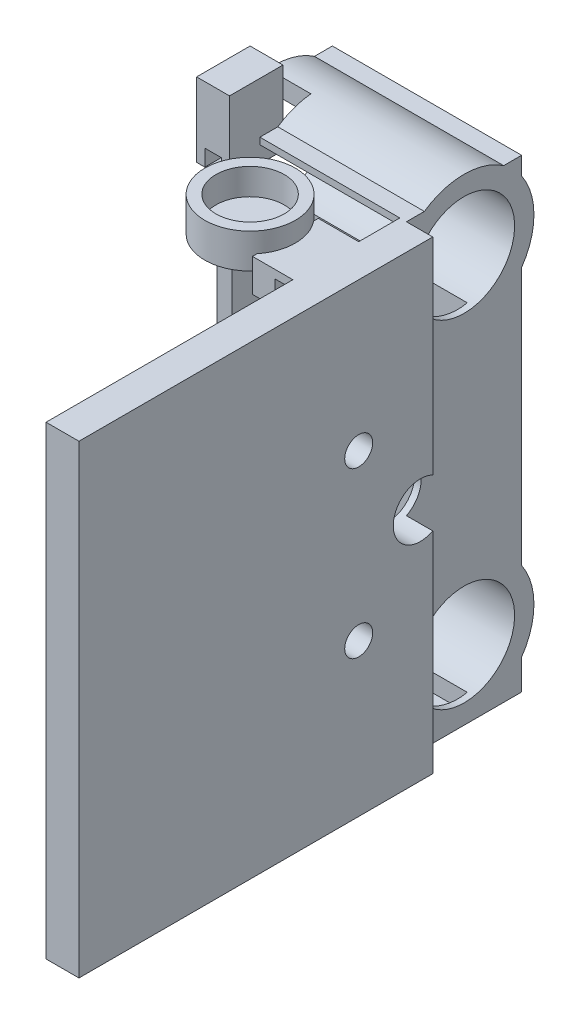
SolidWorks part; units mm, degrees
other "Preload Printed Carriage"
other "Steel core clearance tool"
other "Final core clearance tool"
other "Preload Printed Carriage Left"
ref_plane "Front Plane" through (0, 0, 0) normal (0, 0, 1) x (1, 0, 0)
ref_plane "Top Plane" through (0, 0, 0) normal (0, 1, 0) x (1, 0, 0)
ref_plane "Right Plane" through (0, 0, 0) normal (1, 0, 0) x (0, 0, -1)
sketch3d "Guide carrier body sketch datum points"
  point P0 (27.7083, -57, -35)
  point P1 (37.7083, -57, -35)
  point P2 (27.7083, -47, -35)
ref_plane "Guide carrier body sketch plane" through (0, 0, -35) normal (0, 0, 1) x (1, 0, 0)
sketch "Guide carrier body sketch" plane through (0, 0, -35) normal (0, 0, 1) x (1, 0, 0)
  line L0 (27.7083, -57) -> (50.7083, -57)
  line L1 (50.7083, -57) -> (50.7083, -0.5)
  line L2 (50.7083, -0.5) -> (27.7083, -0.5)
  line L3 (27.7083, -0.5) -> (27.7083, -57)
extrude "Guide carrier body" add sketch "Guide carrier body sketch" along normal blind 14 separate body
sketch3d "Rear clamp wall sketch datum points"
  point P0 (49.9083, -57, -21)
  point P1 (59.9083, -57, -21)
  point P2 (49.9083, -47, -21)
ref_plane "Rear clamp wall sketch plane" through (0, 0, -21) normal (0, 0, 1) x (1, 0, 0)
sketch "Rear clamp wall sketch" plane through (0, 0, -21) normal (0, 0, 1) x (1, 0, 0)
  line L0 (49.9083, -57) -> (53.9083, -57)
  line L1 (53.9083, -57) -> (53.9083, -0.5)
  line L2 (53.9083, -0.5) -> (49.9083, -0.5)
  line L3 (49.9083, -0.5) -> (49.9083, -57)
extrude "Rear clamp wall" add sketch "Rear clamp wall sketch" along normal blind 43
sketch3d "Guide bush boss 1 sketch datum points"
  point P0 (27.7083, -9, -28)
  point P1 (27.7083, 1, -28)
  point P2 (27.7083, -9, -18)
ref_plane "Guide bush boss 1 sketch plane" through (27.7083, 0, 0) normal (1, 0, 0) x (0, 0, -1)
sketch "Guide bush boss 1 sketch" plane through (27.7083, 0, 0) normal (1, 0, 0) x (0, 0, -1)
  circle A0 centre (28, -9) radius 8.5
extrude "Guide bush boss 1" add sketch "Guide bush boss 1 sketch" along normal blind 23
sketch3d "Guide bush boss 2 sketch datum points"
  point P0 (27.7083, -50, -28)
  point P1 (27.7083, -40, -28)
  point P2 (27.7083, -50, -18)
ref_plane "Guide bush boss 2 sketch plane" through (27.7083, 0, 0) normal (1, 0, 0) x (0, 0, -1)
sketch "Guide bush boss 2 sketch" plane through (27.7083, 0, 0) normal (1, 0, 0) x (0, 0, -1)
  circle A0 centre (28, -50) radius 8.5
extrude "Guide bush boss 2" add sketch "Guide bush boss 2 sketch" along normal blind 23
sketch3d "Steel tube cavity sketch datum points"
  point P0 (29.5083, -56.2, -29.2)
  point P1 (39.5083, -56.2, -29.2)
  point P2 (29.5083, -46.2, -29.2)
ref_plane "Steel tube cavity sketch plane" through (0, 0, -29.2) normal (0, 0, 1) x (1, 0, 0)
sketch "Steel tube cavity sketch" plane through (0, 0, -29.2) normal (0, 0, 1) x (1, 0, 0)
  line L0 (29.5083, -56.2) -> (49.9083, -56.2)
  line L1 (49.9083, -56.2) -> (49.9083, -0.8)
  line L2 (49.9083, -0.8) -> (29.5083, -0.8)
  line L3 (29.5083, -0.8) -> (29.5083, -56.2)
extrude "Steel tube cavity" cut sketch "Steel tube cavity sketch" along normal blind 40.4
sketch3d "Guide bush bore 1 sketch datum points"
  point P0 (27.6, -9, -28)
  point P1 (27.6, 1, -28)
  point P2 (27.6, -9, -18)
ref_plane "Guide bush bore 1 sketch plane" through (27.6, 0, 0) normal (1, 0, 0) x (0, 0, -1)
sketch "Guide bush bore 1 sketch" plane through (27.6, 0, 0) normal (1, 0, 0) x (0, 0, -1)
  circle A0 centre (28, -9) radius 6.15
extrude "Guide bush bore 1" cut sketch "Guide bush bore 1 sketch" along normal blind 23.3
sketch3d "Guide bush bore 2 sketch datum points"
  point P0 (27.6, -50, -28)
  point P1 (27.6, -40, -28)
  point P2 (27.6, -50, -18)
ref_plane "Guide bush bore 2 sketch plane" through (27.6, 0, 0) normal (1, 0, 0) x (0, 0, -1)
sketch "Guide bush bore 2 sketch" plane through (27.6, 0, 0) normal (1, 0, 0) x (0, 0, -1)
  circle A0 centre (28, -50) radius 6.15
extrude "Guide bush bore 2" cut sketch "Guide bush bore 2 sketch" along normal blind 23.3
sketch3d "Clamp bolt clearance 1 sketch datum points"
  point P0 (49.8, -19, -12)
  point P1 (49.8, -9, -12)
  point P2 (49.8, -19, -2)
ref_plane "Clamp bolt clearance 1 sketch plane" through (49.8, 0, 0) normal (1, 0, 0) x (0, 0, -1)
sketch "Clamp bolt clearance 1 sketch" plane through (49.8, 0, 0) normal (1, 0, 0) x (0, 0, -1)
  circle A0 centre (12, -19) radius 1.7
extrude "Clamp bolt clearance 1" cut sketch "Clamp bolt clearance 1 sketch" along normal blind 4.3
sketch3d "Clamp bolt clearance 2 sketch datum points"
  point P0 (49.8, -39, -12)
  point P1 (49.8, -29, -12)
  point P2 (49.8, -39, -2)
ref_plane "Clamp bolt clearance 2 sketch plane" through (49.8, 0, 0) normal (1, 0, 0) x (0, 0, -1)
sketch "Clamp bolt clearance 2 sketch" plane through (49.8, 0, 0) normal (1, 0, 0) x (0, 0, -1)
  circle A0 centre (12, -39) radius 1.7
extrude "Clamp bolt clearance 2" cut sketch "Clamp bolt clearance 2 sketch" along normal blind 4.3
sketch3d "Travel flag root sketch datum points"
  point P0 (28.7083, -59, -27)
  point P1 (38.7083, -59, -27)
  point P2 (28.7083, -49, -27)
ref_plane "Travel flag root sketch plane" through (0, 0, -27) normal (0, 0, 1) x (1, 0, 0)
sketch "Travel flag root sketch" plane through (0, 0, -27) normal (0, 0, 1) x (1, 0, 0)
  line L0 (28.7083, -59) -> (32.7083, -59)
  line L1 (32.7083, -59) -> (32.7083, -54)
  line L2 (32.7083, -54) -> (28.7083, -54)
  line L3 (28.7083, -54) -> (28.7083, -59)
extrude "Travel flag root" add sketch "Travel flag root sketch" along normal blind 6
sketch3d "Magnet holder bridge sketch datum points"
  point P0 (45, -57, -16)
  point P1 (55, -57, -16)
  point P2 (45, -47, -16)
ref_plane "Magnet holder bridge sketch plane" through (0, 0, -16) normal (0, 0, 1) x (1, 0, 0)
sketch "Magnet holder bridge sketch" plane through (0, 0, -16) normal (0, 0, 1) x (1, 0, 0)
  line L0 (45, -57) -> (53.908, -57)
  line L1 (53.908, -57) -> (53.908, -53)
  line L2 (53.908, -53) -> (45, -53)
  line L3 (45, -53) -> (45, -57)
extrude "Magnet holder bridge" add sketch "Magnet holder bridge sketch" along normal blind 8
sketch3d "Magnet holder boss sketch datum points"
  point P0 (40.708, -59.4, -12)
  point P1 (50.708, -59.4, -12)
  point P2 (40.708, -59.4, -22)
ref_plane "Magnet holder boss sketch plane" through (0, -59.4, 0) normal (0, 1, 0) x (1, 0, 0)
sketch "Magnet holder boss sketch" plane through (0, -59.4, 0) normal (0, 1, 0) x (1, 0, 0)
  circle A0 centre (40.708, 12) radius 5.5
extrude "Magnet holder boss" add sketch "Magnet holder boss sketch" along normal blind 4.2
sketch3d "Magnet seating pocket sketch datum points"
  point P0 (40.708, -59.5, -12)
  point P1 (50.708, -59.5, -12)
  point P2 (40.708, -59.5, -22)
ref_plane "Magnet seating pocket sketch plane" through (0, -59.5, 0) normal (0, 1, 0) x (1, 0, 0)
sketch "Magnet seating pocket sketch" plane through (0, -59.5, 0) normal (0, 1, 0) x (1, 0, 0)
  circle A0 centre (40.708, 12) radius 4.15
extrude "Magnet seating pocket" cut sketch "Magnet seating pocket sketch" along normal blind 3.3
sketch3d "Steel core clearance tool Steel tube stock sketch datum points"
  point P0 (29.7083, -56, -29)
  point P1 (39.7083, -56, -29)
  point P2 (29.7083, -46, -29)
ref_plane "Steel core clearance tool Steel tube stock sketch plane" through (0, 0, -29) normal (0, 0, 1) x (1, 0, 0)
sketch "Steel core clearance tool Steel tube stock sketch" plane through (0, 0, -29) normal (0, 0, 1) x (1, 0, 0)
  line L0 (29.7083, -56) -> (49.7083, -56)
  line L1 (49.7083, -56) -> (49.7083, -1)
  line L2 (49.7083, -1) -> (29.7083, -1)
  line L3 (29.7083, -1) -> (29.7083, -56)
extrude "Steel core clearance tool Steel tube stock" add sketch "Steel core clearance tool Steel tube stock sketch" along normal blind 40 separate body
sketch3d "Steel core clearance tool Tube interior sketch datum points"
  point P0 (31.7083, -56.1, -27)
  point P1 (41.7083, -56.1, -27)
  point P2 (31.7083, -46.1, -27)
ref_plane "Steel core clearance tool Tube interior sketch plane" through (0, 0, -27) normal (0, 0, 1) x (1, 0, 0)
sketch "Steel core clearance tool Tube interior sketch" plane through (0, 0, -27) normal (0, 0, 1) x (1, 0, 0)
  line L0 (31.7083, -56.1) -> (47.7083, -56.1)
  line L1 (47.7083, -56.1) -> (47.7083, -0.9)
  line L2 (47.7083, -0.9) -> (31.7083, -0.9)
  line L3 (31.7083, -0.9) -> (31.7083, -56.1)
extrude "Steel core clearance tool Tube interior" cut sketch "Steel core clearance tool Tube interior sketch" along normal blind 36
sketch3d "Steel core clearance tool Guide bush clearance 1 sketch datum points"
  point P0 (29.6, -9, -28)
  point P1 (29.6, 1, -28)
  point P2 (29.6, -9, -18)
ref_plane "Steel core clearance tool Guide bush clearance 1 sketch plane" through (29.6, 0, 0) normal (1, 0, 0) x (0, 0, -1)
sketch "Steel core clearance tool Guide bush clearance 1 sketch" plane through (29.6, 0, 0) normal (1, 0, 0) x (0, 0, -1)
  circle A0 centre (28, -9) radius 6.2
extrude "Steel core clearance tool Guide bush clearance 1" cut sketch "Steel core clearance tool Guide bush clearance 1 sketch" along normal blind 20.3
sketch3d "Steel core clearance tool Guide bush clearance 2 sketch datum points"
  point P0 (29.6, -50, -28)
  point P1 (29.6, -40, -28)
  point P2 (29.6, -50, -18)
ref_plane "Steel core clearance tool Guide bush clearance 2 sketch plane" through (29.6, 0, 0) normal (1, 0, 0) x (0, 0, -1)
sketch "Steel core clearance tool Guide bush clearance 2 sketch" plane through (29.6, 0, 0) normal (1, 0, 0) x (0, 0, -1)
  circle A0 centre (28, -50) radius 6.2
extrude "Steel core clearance tool Guide bush clearance 2" cut sketch "Steel core clearance tool Guide bush clearance 2 sketch" along normal blind 20.3
sketch3d "Steel core clearance tool Screw through clearance sketch datum points"
  point P0 (29.6, -29, -19.5)
  point P1 (29.6, -19, -19.5)
  point P2 (29.6, -29, -9.5)
ref_plane "Steel core clearance tool Screw through clearance sketch plane" through (29.6, 0, 0) normal (1, 0, 0) x (0, 0, -1)
sketch "Steel core clearance tool Screw through clearance sketch" plane through (29.6, 0, 0) normal (1, 0, 0) x (0, 0, -1)
  circle A0 centre (19.5, -29) radius 3.3
extrude "Steel core clearance tool Screw through clearance" cut sketch "Steel core clearance tool Screw through clearance sketch" along normal blind 20.3
sketch3d "Steel core clearance tool Spring pin clearance 1 sketch datum points"
  point P0 (35.7083, -12, 8.9)
  point P1 (45.7083, -12, 8.9)
  point P2 (35.7083, -2, 8.9)
ref_plane "Steel core clearance tool Spring pin clearance 1 sketch plane" through (0, 0, 8.9) normal (0, 0, 1) x (1, 0, 0)
sketch "Steel core clearance tool Spring pin clearance 1 sketch" plane through (0, 0, 8.9) normal (0, 0, 1) x (1, 0, 0)
  circle A0 centre (35.7083, -12) radius 1.7
extrude "Steel core clearance tool Spring pin clearance 1" cut sketch "Steel core clearance tool Spring pin clearance 1 sketch" along normal blind 2.2
sketch3d "Steel core clearance tool Spring pin clearance 2 sketch datum points"
  point P0 (35.7083, -29, 8.9)
  point P1 (45.7083, -29, 8.9)
  point P2 (35.7083, -19, 8.9)
ref_plane "Steel core clearance tool Spring pin clearance 2 sketch plane" through (0, 0, 8.9) normal (0, 0, 1) x (1, 0, 0)
sketch "Steel core clearance tool Spring pin clearance 2 sketch" plane through (0, 0, 8.9) normal (0, 0, 1) x (1, 0, 0)
  circle A0 centre (35.7083, -29) radius 1.7
extrude "Steel core clearance tool Spring pin clearance 2" cut sketch "Steel core clearance tool Spring pin clearance 2 sketch" along normal blind 2.2
sketch3d "Steel core clearance tool Spring pin clearance 3 sketch datum points"
  point P0 (35.7083, -46, 8.9)
  point P1 (45.7083, -46, 8.9)
  point P2 (35.7083, -36, 8.9)
ref_plane "Steel core clearance tool Spring pin clearance 3 sketch plane" through (0, 0, 8.9) normal (0, 0, 1) x (1, 0, 0)
sketch "Steel core clearance tool Spring pin clearance 3 sketch" plane through (0, 0, 8.9) normal (0, 0, 1) x (1, 0, 0)
  circle A0 centre (35.7083, -46) radius 1.7
extrude "Steel core clearance tool Spring pin clearance 3" cut sketch "Steel core clearance tool Spring pin clearance 3 sketch" along normal blind 2.2
sketch3d "Steel core clearance tool Clamp bolt clearance 1 sketch datum points"
  point P0 (47.6, -19, -12)
  point P1 (47.6, -9, -12)
  point P2 (47.6, -19, -2)
ref_plane "Steel core clearance tool Clamp bolt clearance 1 sketch plane" through (47.6, 0, 0) normal (1, 0, 0) x (0, 0, -1)
sketch "Steel core clearance tool Clamp bolt clearance 1 sketch" plane through (47.6, 0, 0) normal (1, 0, 0) x (0, 0, -1)
  circle A0 centre (12, -19) radius 1.7
extrude "Steel core clearance tool Clamp bolt clearance 1" cut sketch "Steel core clearance tool Clamp bolt clearance 1 sketch" along normal blind 2.3
sketch3d "Steel core clearance tool Clamp bolt clearance 2 sketch datum points"
  point P0 (47.6, -39, -12)
  point P1 (47.6, -29, -12)
  point P2 (47.6, -39, -2)
ref_plane "Steel core clearance tool Clamp bolt clearance 2 sketch plane" through (47.6, 0, 0) normal (1, 0, 0) x (0, 0, -1)
sketch "Steel core clearance tool Clamp bolt clearance 2 sketch" plane through (47.6, 0, 0) normal (1, 0, 0) x (0, 0, -1)
  circle A0 centre (12, -39) radius 1.7
extrude "Steel core clearance tool Clamp bolt clearance 2" cut sketch "Steel core clearance tool Clamp bolt clearance 2 sketch" along normal blind 2.3
combine bodies "Combine1" operation type subtract main body 113 bodies to subtract 123
sketch3d "Screw full travel clearance sketch datum points"
  point P0 (27.5, -29, -19.5)
  point P1 (27.5, -19, -19.5)
  point P2 (27.5, -29, -9.5)
ref_plane "Screw full travel clearance sketch plane" through (27.5, 0, 0) normal (1, 0, 0) x (0, 0, -1)
sketch "Screw full travel clearance sketch" plane through (27.5, 0, 0) normal (1, 0, 0) x (0, 0, -1)
  circle A0 centre (19.5, -29) radius 3.3
extrude "Screw full travel clearance" cut sketch "Screw full travel clearance sketch" along normal blind 26.7
sketch3d "Travel flag relief sketch datum points"
  point P0 (28.6, -59.2, -27.2)
  point P1 (38.6, -59.2, -27.2)
  point P2 (28.6, -49.2, -27.2)
ref_plane "Travel flag relief sketch plane" through (0, 0, -27.2) normal (0, 0, 1) x (1, 0, 0)
sketch "Travel flag relief sketch" plane through (0, 0, -27.2) normal (0, 0, 1) x (1, 0, 0)
  line L0 (28.6, -59.2) -> (32.9, -59.2)
  line L1 (32.9, -59.2) -> (32.9, -54)
  line L2 (32.9, -54) -> (28.6, -54)
  line L3 (28.6, -54) -> (28.6, -59.2)
extrude "Travel flag relief" cut sketch "Travel flag relief sketch" along normal blind 6.3
sketch3d "Clearanced travel flag sketch datum points"
  point P0 (28.7083, 0, 0)
  point P1 (28.7083, 10, 0)
  point P2 (28.7083, 0, 10)
ref_plane "Clearanced travel flag sketch plane" through (28.7083, 0, 0) normal (1, 0, 0) x (0, 0, -1)
sketch "Clearanced travel flag sketch" plane through (28.7083, 0, 0) normal (1, 0, 0) x (0, 0, -1)
  line L0 (17.5, -63) -> (24, -63)
  line L1 (24, -63) -> (24, -54.6715)
  line L2 (23.3285, -54) -> (17.5, -54)
  line L3 (17.5, -54) -> (17.5, -63)
  arc A0 (24, -54.6715) -> (23.3285, -54) centre (28, -50) cw
extrude "Clearanced travel stop flag" add sketch "Clearanced travel flag sketch" along normal blind 4
sketch3d "Final core clearance tool Steel tube stock sketch datum points"
  point P0 (29.7083, -56, -29)
  point P1 (39.7083, -56, -29)
  point P2 (29.7083, -46, -29)
ref_plane "Final core clearance tool Steel tube stock sketch plane" through (0, 0, -29) normal (0, 0, 1) x (1, 0, 0)
sketch "Final core clearance tool Steel tube stock sketch" plane through (0, 0, -29) normal (0, 0, 1) x (1, 0, 0)
  line L0 (29.7083, -56) -> (49.7083, -56)
  line L1 (49.7083, -56) -> (49.7083, -1)
  line L2 (49.7083, -1) -> (29.7083, -1)
  line L3 (29.7083, -1) -> (29.7083, -56)
extrude "Final core clearance tool Steel tube stock" add sketch "Final core clearance tool Steel tube stock sketch" along normal blind 40 separate body
sketch3d "Final core clearance tool Tube interior sketch datum points"
  point P0 (31.7083, -56.1, -27)
  point P1 (41.7083, -56.1, -27)
  point P2 (31.7083, -46.1, -27)
ref_plane "Final core clearance tool Tube interior sketch plane" through (0, 0, -27) normal (0, 0, 1) x (1, 0, 0)
sketch "Final core clearance tool Tube interior sketch" plane through (0, 0, -27) normal (0, 0, 1) x (1, 0, 0)
  line L0 (31.7083, -56.1) -> (47.7083, -56.1)
  line L1 (47.7083, -56.1) -> (47.7083, -0.9)
  line L2 (47.7083, -0.9) -> (31.7083, -0.9)
  line L3 (31.7083, -0.9) -> (31.7083, -56.1)
extrude "Final core clearance tool Tube interior" cut sketch "Final core clearance tool Tube interior sketch" along normal blind 36
sketch3d "Final core clearance tool Guide bush clearance 1 sketch datum points"
  point P0 (29.6, -9, -28)
  point P1 (29.6, 1, -28)
  point P2 (29.6, -9, -18)
ref_plane "Final core clearance tool Guide bush clearance 1 sketch plane" through (29.6, 0, 0) normal (1, 0, 0) x (0, 0, -1)
sketch "Final core clearance tool Guide bush clearance 1 sketch" plane through (29.6, 0, 0) normal (1, 0, 0) x (0, 0, -1)
  circle A0 centre (28, -9) radius 6.2
extrude "Final core clearance tool Guide bush clearance 1" cut sketch "Final core clearance tool Guide bush clearance 1 sketch" along normal blind 20.3
sketch3d "Final core clearance tool Guide bush clearance 2 sketch datum points"
  point P0 (29.6, -50, -28)
  point P1 (29.6, -40, -28)
  point P2 (29.6, -50, -18)
ref_plane "Final core clearance tool Guide bush clearance 2 sketch plane" through (29.6, 0, 0) normal (1, 0, 0) x (0, 0, -1)
sketch "Final core clearance tool Guide bush clearance 2 sketch" plane through (29.6, 0, 0) normal (1, 0, 0) x (0, 0, -1)
  circle A0 centre (28, -50) radius 6.2
extrude "Final core clearance tool Guide bush clearance 2" cut sketch "Final core clearance tool Guide bush clearance 2 sketch" along normal blind 20.3
sketch3d "Final core clearance tool Screw through clearance sketch datum points"
  point P0 (29.6, -29, -19.5)
  point P1 (29.6, -19, -19.5)
  point P2 (29.6, -29, -9.5)
ref_plane "Final core clearance tool Screw through clearance sketch plane" through (29.6, 0, 0) normal (1, 0, 0) x (0, 0, -1)
sketch "Final core clearance tool Screw through clearance sketch" plane through (29.6, 0, 0) normal (1, 0, 0) x (0, 0, -1)
  circle A0 centre (19.5, -29) radius 3.3
extrude "Final core clearance tool Screw through clearance" cut sketch "Final core clearance tool Screw through clearance sketch" along normal blind 20.3
sketch3d "Final core clearance tool Spring pin clearance 1 sketch datum points"
  point P0 (35.7083, -12, 8.9)
  point P1 (45.7083, -12, 8.9)
  point P2 (35.7083, -2, 8.9)
ref_plane "Final core clearance tool Spring pin clearance 1 sketch plane" through (0, 0, 8.9) normal (0, 0, 1) x (1, 0, 0)
sketch "Final core clearance tool Spring pin clearance 1 sketch" plane through (0, 0, 8.9) normal (0, 0, 1) x (1, 0, 0)
  circle A0 centre (35.7083, -12) radius 1.7
extrude "Final core clearance tool Spring pin clearance 1" cut sketch "Final core clearance tool Spring pin clearance 1 sketch" along normal blind 2.2
sketch3d "Final core clearance tool Spring pin clearance 2 sketch datum points"
  point P0 (35.7083, -29, 8.9)
  point P1 (45.7083, -29, 8.9)
  point P2 (35.7083, -19, 8.9)
ref_plane "Final core clearance tool Spring pin clearance 2 sketch plane" through (0, 0, 8.9) normal (0, 0, 1) x (1, 0, 0)
sketch "Final core clearance tool Spring pin clearance 2 sketch" plane through (0, 0, 8.9) normal (0, 0, 1) x (1, 0, 0)
  circle A0 centre (35.7083, -29) radius 1.7
extrude "Final core clearance tool Spring pin clearance 2" cut sketch "Final core clearance tool Spring pin clearance 2 sketch" along normal blind 2.2
sketch3d "Final core clearance tool Spring pin clearance 3 sketch datum points"
  point P0 (35.7083, -46, 8.9)
  point P1 (45.7083, -46, 8.9)
  point P2 (35.7083, -36, 8.9)
ref_plane "Final core clearance tool Spring pin clearance 3 sketch plane" through (0, 0, 8.9) normal (0, 0, 1) x (1, 0, 0)
sketch "Final core clearance tool Spring pin clearance 3 sketch" plane through (0, 0, 8.9) normal (0, 0, 1) x (1, 0, 0)
  circle A0 centre (35.7083, -46) radius 1.7
extrude "Final core clearance tool Spring pin clearance 3" cut sketch "Final core clearance tool Spring pin clearance 3 sketch" along normal blind 2.2
sketch3d "Final core clearance tool Clamp bolt clearance 1 sketch datum points"
  point P0 (47.6, -19, -12)
  point P1 (47.6, -9, -12)
  point P2 (47.6, -19, -2)
ref_plane "Final core clearance tool Clamp bolt clearance 1 sketch plane" through (47.6, 0, 0) normal (1, 0, 0) x (0, 0, -1)
sketch "Final core clearance tool Clamp bolt clearance 1 sketch" plane through (47.6, 0, 0) normal (1, 0, 0) x (0, 0, -1)
  circle A0 centre (12, -19) radius 1.7
extrude "Final core clearance tool Clamp bolt clearance 1" cut sketch "Final core clearance tool Clamp bolt clearance 1 sketch" along normal blind 2.3
sketch3d "Final core clearance tool Clamp bolt clearance 2 sketch datum points"
  point P0 (47.6, -39, -12)
  point P1 (47.6, -29, -12)
  point P2 (47.6, -39, -2)
ref_plane "Final core clearance tool Clamp bolt clearance 2 sketch plane" through (47.6, 0, 0) normal (1, 0, 0) x (0, 0, -1)
sketch "Final core clearance tool Clamp bolt clearance 2 sketch" plane through (47.6, 0, 0) normal (1, 0, 0) x (0, 0, -1)
  circle A0 centre (12, -39) radius 1.7
extrude "Final core clearance tool Clamp bolt clearance 2" cut sketch "Final core clearance tool Clamp bolt clearance 2 sketch" along normal blind 2.3
combine bodies "Combine2" operation type subtract main body 127 bodies to subtract 137
sketch3d "Mirror1 profile datum points"
  point P0 (0, 0, 0)
  point P1 (10, 0, 0)
  point P2 (0, 0, 10)
ref_plane "Mirror1 profile plane" through (0, 0, 0) normal (0, -1, 0) x (-1, 0, 0)
mirror "Mirror1" about plane through (0, 0, 0) normal (0, -1, 0) of bodies 138
delete or keep bodies "Remove1" type delete bodies bodies 138
